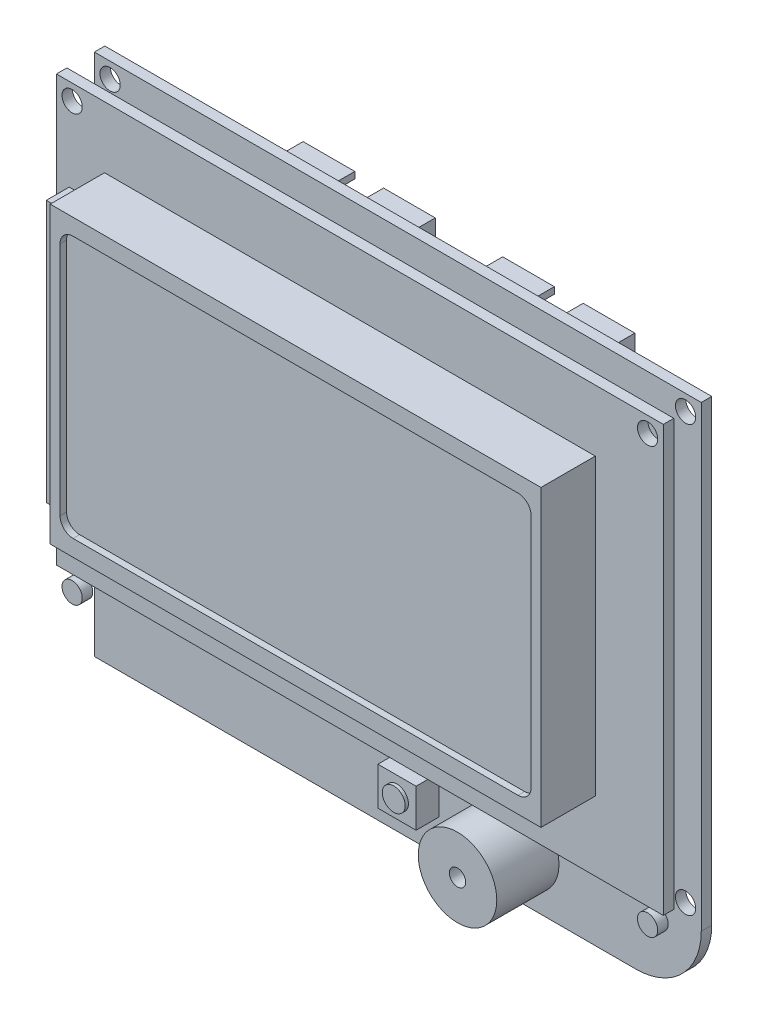
SolidWorks part; units mm, degrees
ref_plane "Front Plane" through (0, 0, 0) normal (0, 0, 1) x (1, 0, 0)
ref_plane "Top Plane" through (0, 0, 0) normal (0, 1, 0) x (1, 0, 0)
ref_plane "Right Plane" through (0, 0, 0) normal (1, 0, 0) x (0, 0, -1)
sketch "Sketch1" plane through (0, 0, 0) normal (0, 0, 1) x (1, 0, 0)
  line L1 (-46.375, -40) -> (46.375, -40)
  line L2 (-46.375, -40) -> (-46.375, 40)
  line L3 (-46.375, 40) -> (46.375, 40)
  line L4 (46.375, -40) -> (46.375, 40)
  line L6 (-43.975, 37.6) -> (43.975, 37.6) construction
  line L7 (-43.975, 37.6) -> (-43.975, -27.4) construction
  line L8 (-43.975, -27.4) -> (43.975, -27.4) construction
  line L9 (43.975, 37.6) -> (43.975, -27.4) construction
  circle A0 centre (-43.975, 37.6) radius 1.55
  circle A1 centre (43.975, 37.6) radius 1.55
  circle A2 centre (43.975, -27.4) radius 1.55
  circle A3 centre (-43.975, -27.4) radius 1.55
  point P5 (0, 40)
  point P6 (-46.375, 0)
  dimension "D3" = 3.1
  dimension "D1" = 80
  dimension "D2" = 92.75
  dimension "D4" = 2.4
  dimension "D5" = 2.4
  dimension "D6" = 2.4
  dimension "D7" = 65
extrude "Boss-Extrude1 - First PCB" add sketch "Sketch1" along normal blind 1.6
sketch "Sketch2" plane through (0, 0, 1.6) normal (0, 0, 1) x (1, 0, 0)
  line L0 (-46.375, -40) -> (46.375, -40) construction
  line L1 (-46.375, -40) -> (-46.375, 40) construction
  circle A0 centre (18.625, -32) radius 6
  dimension "D1" = 12
  dimension "D2" = 8
  dimension "D3" = 65
extrude "Boss-Extrude2 - Speaker" add sketch "Sketch2" along normal blind 9.5
sketch "Sketch15" plane through (0, 0, 11.1) normal (0, 0, 1) x (1, 0, 0)
  circle A0 centre (18.625, -32) radius 1.25
  dimension "D1" = 2.5
extrude "Cut-Extrude1 - Speaker Hole" cut sketch "Sketch15" against normal blind 5
sketch "Sketch3" plane through (0, 0, 1.6) normal (0, 0, 1) x (-1, 0, 0)
  line L1 (-42.375, 37.825) -> (-30.375, 37.825)
  line L2 (-42.375, 37.825) -> (-42.375, 26.175)
  line L3 (-42.375, 26.175) -> (-30.375, 26.175)
  line L4 (-30.375, 37.825) -> (-30.375, 26.175)
  line L8 (-30.375, 32) -> (-18.625, 32) construction
  line L10 (-36.375, 37.825) -> (-36.375, 26.175) construction
  line L11 (-46.375, 40) -> (-46.375, -40) construction
  circle A1 centre (-18.625, 32) radius 6 construction
  point P19 (-12.6367, 31.6254)
  dimension "D1" = 11.65
  dimension "D2" = 12
  dimension "D3" = 10
sketch "Sketch4" plane through (0, 0, 1.6) normal (0, 0, 1) x (-1, 0, 0)
  line L0 (-3.375, 34.915) -> (-3.375, 29.085) construction
  line L1 (-6.29, 34.915) -> (-0.46, 34.915)
  line L2 (-6.29, 34.915) -> (-6.29, 29.085)
  line L3 (-6.29, 29.085) -> (-0.46, 29.085)
  line L4 (-0.46, 34.915) -> (-0.46, 29.085)
  line L5 (-6.29, 32) -> (-0.46, 32) construction
  line L6 (-6.29, 32) -> (-18.625, 32) construction
  line L15 (-46.375, 40) -> (-46.375, -40) construction
  point P8 (-3.375, 32)
  dimension "D1" = 5.83
  dimension "D2" = 5.83
  dimension "D3" = 43
extrude "Boss-Extrude4 - Reset Switch" add sketch "Sketch4" along normal blind 3.5
sketch "Sketch5" plane through (0, 0, 5.1) normal (0, 0, 1) x (-1, 0, 0)
  line L1 (-6.29, 34.915) -> (-0.46, 29.085) construction
  line L2 (-0.46, 34.915) -> (-6.29, 29.085) construction
  circle A0 centre (-3.375, 32) radius 1.75
  dimension "D1" = 3.5
extrude "Boss-Extrude5 - Reset Button" add sketch "Sketch5" along normal blind 0.5
sketch "Sketch19" plane through (0, 0, 1.6) normal (0, 0, 1) x (1, 0, 0)
  line L0 (-46.375, 40) -> (-46.375, -40) construction
  line L1 (-33.375, -19.5) -> (16.625, -19.5)
  line L2 (-33.375, -19.5) -> (-33.375, -22)
  line L3 (-33.375, -22) -> (16.625, -22)
  line L4 (16.625, -19.5) -> (16.625, -22)
  line L5 (-46.375, -40) -> (46.375, -40) construction
  dimension "D1" = 2.5
  dimension "D2" = 50
  dimension "D3" = 13
  dimension "D4" = 18
extrude "Boss-Extrude10 - Connector" add sketch "Sketch19" along normal blind 4.2
sketch "Sketch11" plane through (0, -2, 5.8) normal (0, 0, -1) x (1, 0, 0)
  line L1 (46.375, 23) -> (-46.375, 23)
  line L2 (46.375, 23) -> (46.375, -42)
  line L3 (46.375, -42) -> (-46.375, -42)
  line L4 (-46.375, 23) -> (-46.375, -42)
  line L8 (46.375, 38) -> (46.375, -42) construction
  circle A0 centre (-43.975, -39.6) radius 1.55 construction
  circle A1 centre (-43.975, -39.6) radius 1.55
  circle A2 centre (-43.975, 25.4) radius 1.55 construction
  circle A3 centre (43.975, -39.6) radius 1.55 construction
  circle A4 centre (43.975, 25.4) radius 1.55 construction
  circle A5 centre (-43.975, 25.4) radius 1.55
  circle A6 centre (43.975, -39.6) radius 1.55
  circle A7 centre (43.975, 25.4) radius 1.55
  dimension "D2" = 65
extrude "Boss-Extrude11 - Upper PCB" add sketch "Sketch11" against normal blind 1.6
sketch "Sketch12" plane through (0, 0, 7.4) normal (0, 0, 1) x (-1, 0, 0)
  line L1 (-35.975, 14.4) -> (39.025, 14.4)
  line L2 (-35.975, 14.4) -> (-35.975, -30.6)
  line L3 (-35.975, -30.6) -> (39.025, -30.6)
  line L4 (39.025, 14.4) -> (39.025, -30.6)
  line L6 (46.375, -40) -> (-46.375, -40) construction
  line L7 (46.375, 25) -> (46.375, -40) construction
  dimension "D1" = 45
  dimension "D2" = 75
  dimension "D3" = 9.4
  dimension "D4" = 7.35
extrude "Boss-Extrude12 - LCD" add sketch "Sketch12" along normal blind 8.3
sketch "Sketch24" plane through (0, 0, 7.4) normal (0, 0, 1) x (1, 0, 0)
  line L0 (-39.025, 30.6) -> (-39.025, -14.4) construction
  line L1 (-39.025, 26) -> (-44.425, 26)
  line L2 (-39.025, 26) -> (-39.025, -14)
  line L3 (-39.025, -14) -> (-44.425, -14)
  line L4 (-44.425, 26) -> (-44.425, -14)
  line L5 (35.975, 30.6) -> (-39.025, 30.6) construction
  dimension "D1" = 5.4
  dimension "D2" = 40
  dimension "D3" = 4.6
extrude "Boss-Extrude13 - LCD Bumpout" add sketch "Sketch24" along normal blind 3.5
sketch "Sketch13" plane through (0, 0, 15.7) normal (0, 0, 1) x (-1, 0, 0)
  line L0 (1.525, 14.4) -> (1.525, -30.6) construction
  line L2 (-35.975, -30.6) -> (39.025, -30.6) construction
  line L3 (-35.975, -8.1) -> (39.025, -8.1) construction
  line L4 (-35.975, 14.4) -> (-35.975, -30.6) construction
  line L5 (39.025, -30.6) -> (39.025, 14.4) construction
  line L6 (1.525, 11.9) -> (1.525, -28.1) construction
  line L7 (-32.475, 11.9) -> (35.525, 11.9)
  line L8 (-34.475, 9.9) -> (-34.475, -26.1)
  line L9 (-32.475, -28.1) -> (35.525, -28.1)
  line L10 (37.525, 9.9) -> (37.525, -26.1)
  line L11 (-35.975, 14.4) -> (39.025, 14.4) construction
  arc A8 (35.525, 11.9) -> (37.525, 9.9) centre (35.525, 9.9) cw
  arc A9 (-34.475, -26.1) -> (-32.475, -28.1) centre (-32.475, -26.1) ccw
  arc A10 (-32.475, 11.9) -> (-34.475, 9.9) centre (-32.475, 9.9) ccw
  arc A11 (35.525, -28.1) -> (37.525, -26.1) centre (35.525, -26.1) ccw
  point P18 (1.525, -8.1)
  point P19 (1.525, -8.1)
  point P62 (-34.475, -28.1)
  point P65 (-34.475, 11.9)
  dimension "D8" = 2
  dimension "D1" = 40
  dimension "D2" = 72
extrude "Cut-Extrude2 - Screen Recess" cut sketch "Sketch13" against normal blind 1 contours L10 L7 L8 L9 region at (-1.525, 8.1, 15.7)
sketch "Sketch21" plane through (0, 0, 0) normal (0, 0, -1) x (-1, 0, 0)
  line L0 (-46.375, -40) -> (-46.375, 40) construction
  line L1 (-25.625, 33.5) -> (-5.425, 33.5)
  line L2 (-25.625, 33.5) -> (-25.625, 24.65)
  line L3 (-25.625, 24.65) -> (-5.425, 24.65)
  line L4 (-5.425, 33.5) -> (-5.425, 24.65)
  line L5 (4.875, 33.5) -> (25.075, 33.5)
  line L6 (4.875, 33.5) -> (4.875, 24.65)
  line L7 (4.875, 24.65) -> (25.075, 24.65)
  line L8 (25.075, 33.5) -> (25.075, 24.65)
  line L9 (-46.375, 40) -> (46.375, 40) construction
  line L10 (-24.625, 32.5) -> (-6.425, 32.5)
  line L11 (-6.425, 32.5) -> (-6.425, 25.65)
  line L12 (-24.625, 25.65) -> (-6.425, 25.65)
  line L13 (-24.625, 32.5) -> (-24.625, 25.65)
  line L14 (5.875, 32.5) -> (24.075, 32.5)
  line L15 (24.075, 32.5) -> (24.075, 25.65)
  line L16 (5.875, 25.65) -> (24.075, 25.65)
  line L17 (5.875, 32.5) -> (5.875, 25.65)
  dimension "D1" = 20.2
  dimension "D2" = 10.3
  dimension "D3" = 8.85
  dimension "D4" = 20.75
  dimension "D5" = 6.5
  dimension "D6" = 1
  dimension "D7" = 1
extrude "Boss-Extrude14 - Connectors" add sketch "Sketch21" along normal blind 9
sketch "Sketch22" plane through (0, 0, 0) normal (0, 0, -1) x (-1, 0, 0)
  line L4 (-24.625, 32.5) -> (-24.625, 25.65)
  line L5 (-24.625, 25.65) -> (-6.425, 25.65)
  line L6 (-6.425, 25.65) -> (-6.425, 32.5)
  line L7 (-6.425, 32.5) -> (-24.625, 32.5)
  line L8 (-24.625, 32.5) -> (-24.625, 25.65)
  line L9 (-24.625, 25.65) -> (-6.425, 25.65)
  line L10 (-6.425, 25.65) -> (-6.425, 32.5)
  line L11 (-6.425, 32.5) -> (-24.625, 32.5)
  line L12 (5.875, 32.5) -> (5.875, 25.65)
  line L13 (5.875, 25.65) -> (24.075, 25.65)
  line L14 (24.075, 25.65) -> (24.075, 32.5)
  line L15 (24.075, 32.5) -> (5.875, 32.5)
  line L16 (5.875, 32.5) -> (5.875, 25.65)
  line L17 (5.875, 25.65) -> (24.075, 25.65)
  line L18 (24.075, 25.65) -> (24.075, 32.5)
  line L19 (24.075, 32.5) -> (5.875, 32.5)
  dimension "D1" = 0
  dimension "D2" = 0
extrude "Boss-Extrude15 - Connector Recess" add sketch "Sketch22" along normal blind 2.55
sketch "Sketch23" plane through (0, 0, -9) normal (0, 0, -1) x (-1, 0, 0)
  line L0 (-5.425, 33.5) -> (-25.625, 33.5) construction
  line L1 (-17.725, 33.5) -> (-13.325, 33.5)
  line L2 (-17.725, 33.5) -> (-17.725, 32.5)
  line L3 (-17.725, 32.5) -> (-13.325, 32.5)
  line L4 (-13.325, 33.5) -> (-13.325, 32.5)
  line L5 (-6.425, 32.5) -> (-24.625, 32.5) construction
  line L6 (25.075, 33.5) -> (4.875, 33.5) construction
  line L7 (12.775, 33.5) -> (17.175, 33.5)
  line L8 (12.775, 33.5) -> (12.775, 32.5)
  line L9 (12.775, 32.5) -> (17.175, 32.5)
  line L10 (17.175, 33.5) -> (17.175, 32.5)
  line L11 (24.075, 32.5) -> (5.875, 32.5) construction
  line L12 (14.975, 25.65) -> (14.975, 33.5) construction
  line L13 (5.875, 25.65) -> (24.075, 25.65) construction
  line L14 (-15.525, 25.65) -> (-15.525, 33.5) construction
  line L15 (-24.625, 25.65) -> (-6.425, 25.65) construction
  point P20 (14.975, 33.5)
  point P25 (-15.525, 33.5)
  dimension "D1" = 4.4
extrude "Cut-Extrude3 - Connector Notch" cut sketch "Sketch23" against normal up to surface (6.45 mm away) up to face at (15.525, 29.075, -2.55)
fillet "Fillet1" radius 10 1 edges at (46.375, -40, 0.8)
